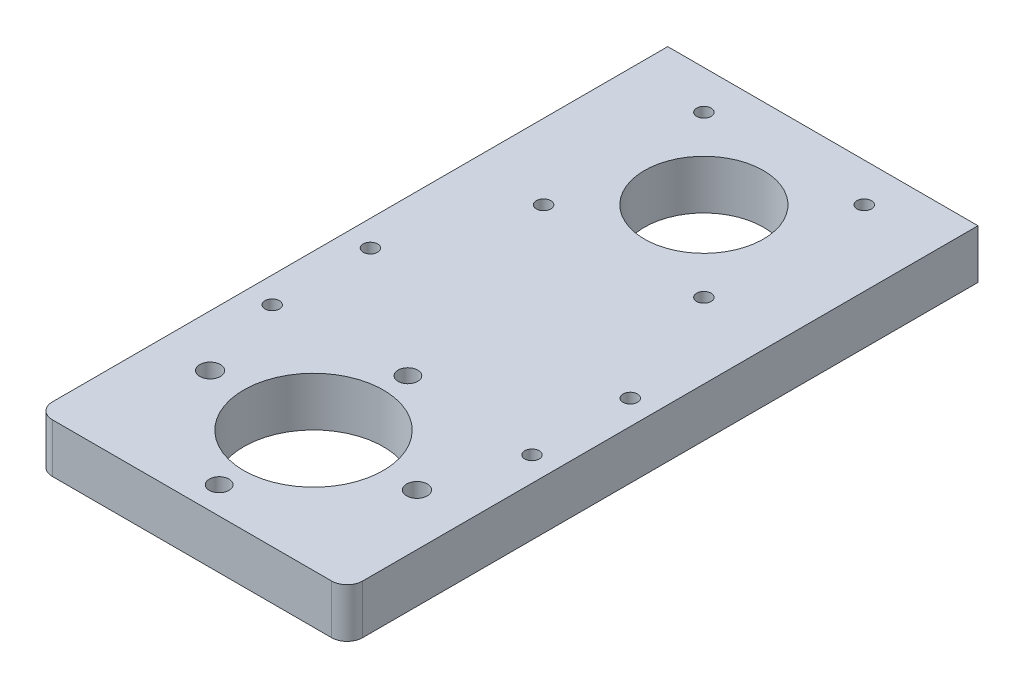
SolidWorks part; units mm, degrees
ref_plane "前视基准面" through (0, 0, 0) normal (0, 0, 1) x (1, 0, 0)
ref_plane "上视基准面" through (0, 0, 0) normal (0, 1, 0) x (1, 0, 0)
ref_plane "右视基准面" through (0, 0, 0) normal (1, 0, 0) x (0, 0, -1)
sketch "草图1" plane through (0, 0, 0) normal (0, 1, 0) x (1, 0, 0)
  line L1 (-29.9577, 29.1823) -> (30.0423, 29.1823)
  line L2 (-29.9577, 29.1823) -> (-29.9577, -33.8177)
  line L3 (-29.9577, -33.8177) -> (30.0423, -33.8177)
  line L4 (30.0423, 29.1823) -> (30.0423, -33.8177)
  line L5 (-29.9577, 29.1823) -> (30.0423, -33.8177) construction
  line L6 (-29.9577, -33.8177) -> (30.0423, 29.1823) construction
  circle A0 centre (0.0423, -10.3177) radius 8 construction
  point P0 (0.0423, -2.3177)
  dimension "D1" = 63
  dimension "D2" = 60
extrude "凸台-拉伸1" add sketch "草图1" along normal blind 9.5
fillet "圆角1" radius 3 2 edges at (30.0423, 4.75, 33.8177) (-29.9577, 4.75, 33.8177)
sketch "草图3" plane through (0, 9.5, 0) normal (0, 1, 0) x (1, 0, 0)
  circle A0 centre (0.0423, -10.3177) radius 13.5
  dimension "D1" = 27
extrude "切除-拉伸2" cut sketch "草图3" against normal through all
sketch "草图5" plane through (0, 9.5, 0) normal (0, 1, 0) x (1, 0, 0)
  circle A0 centre (25.2923, 25.6852) radius 1.4
  circle A1 centre (25.2923, 6.6852) radius 1.4
  circle A2 centre (-24.9577, 25.6852) radius 1.4
  circle A4 centre (-24.9577, 6.6852) radius 1.4
  dimension "D1" = 2.8
extrude "切除-拉伸4" cut sketch "草图5" against normal through all
sketch "草图7" plane through (0, 0, 0) normal (0, -1, 0) x (1, 0, 0)
  circle A0 centre (-19.9577, 10.3148) radius 4
  circle A1 centre (20.0423, 10.3148) radius 4
  dimension "D1" = 8
extrude "切除-拉伸6" cut sketch "草图7" against normal blind 4.5
sketch "草图8" plane through (0, 9.5, 0) normal (0, 1, 0) x (1, 0, 0)
  circle A0 centre (-19.9577, -10.3148) radius 2
  circle A1 centre (20.0423, -10.3148) radius 2
  dimension "D1" = 4
extrude "切除-拉伸7" cut sketch "草图8" against normal through all
sketch "草图10" plane through (0, 9.5, 0) normal (0, 1, 0) x (1, 0, 0)
  circle A0 centre (0.0423, 7.9323) radius 1.9
  circle A1 centre (0.0423, -28.5677) radius 1.9
  dimension "D1" = 3.8
extrude "切除-拉伸9" cut sketch "草图10" against normal through all
ref_plane "基准面1" through (0.0423, 0, 0) normal (1, 0, 0) x (0, 0, -1)
ref_plane "基准面2" through (-29.9577, 9.5, -29.1823) normal (0, 0, 1) x (1, 0, 0)
ref_plane "基准面3" through (0, 0, -29.1823) normal (0, 0, -1) x (-1, 0, 0)
sketch "草图11" plane through (0, 0, -29.1823) normal (0, 0, -1) x (-1, 0, 0)
  line L0 (-30.0423, 0) -> (29.9577, 0) construction
  line L1 (-30.0423, 9.5) -> (29.9577, 9.5)
  line L2 (-30.0423, 9.5) -> (-30.0423, 0)
  line L3 (-30.0423, 0) -> (29.9577, 0)
  line L4 (29.9577, 9.5) -> (29.9577, 0)
extrude "凸台-拉伸2" add sketch "草图11" along normal blind 59
sketch "草图12" plane through (0, 0, 0) normal (0, -1, 0) x (1, 0, 0)
  circle A0 centre (0.0339, -65.1831) radius 11.5
  dimension "D1" = 23
extrude "切除-拉伸10" cut sketch "草图12" against normal through all
sketch "草图13" plane through (0, 0, 0) normal (0, -1, 0) x (1, 0, 0)
  circle A0 centre (-15.4661, -49.6831) radius 1.4
  circle A1 centre (-15.4661, -80.6831) radius 1.4
  circle A2 centre (15.5339, -80.6831) radius 1.4
  circle A3 centre (15.5339, -49.6831) radius 1.4
  dimension "D1" = 2.8
extrude "切除-拉伸11" cut sketch "草图13" against normal through all
sketch "草图15" plane through (0, 0, 0) normal (0, -1, 0) x (1, 0, 0)
  circle A0 centre (-24.9577, -6.6852) radius 3.4
  circle A1 centre (-24.9577, -25.6852) radius 3.4
  circle A2 centre (25.2923, -6.6852) radius 3.4
  circle A3 centre (25.2923, -25.6852) radius 3.4
  dimension "D1" = 6.8
extrude "切除-拉伸13" cut sketch "草图15" against normal blind 4.5
